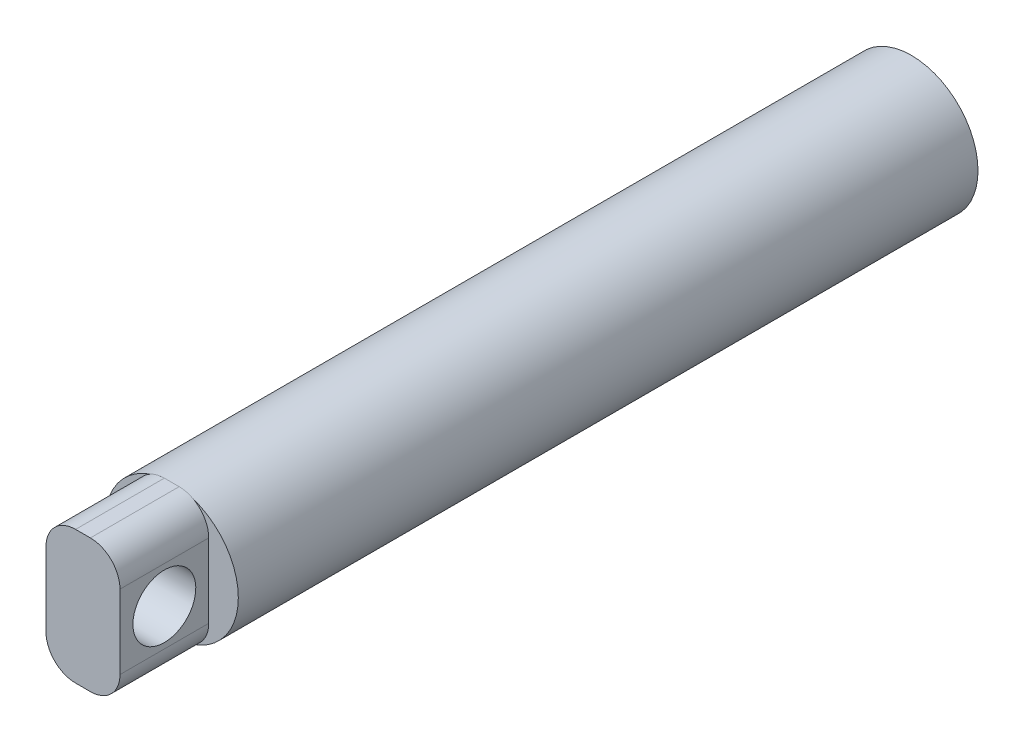
SolidWorks part; units mm, degrees
ref_plane "Plano frontal" through (0, 0, 0) normal (0, 0, 1) x (1, 0, 0)
ref_plane "Plano superior" through (0, 0, 0) normal (0, 1, 0) x (1, 0, 0)
ref_plane "Plano direito" through (0, 0, 0) normal (1, 0, 0) x (0, 0, -1)
sketch "Esboço1" plane through (0, 0, 0) normal (0, 0, 1) x (1, 0, 0)
  circle A0 centre (0, 0) radius 4.5
  dimension "D1" = 9
extrude "Ressalto-extrusão1" add sketch "Esboço1" along normal blind 50
sketch "Esboço2" plane through (0, 0, 50) normal (0, 0, 1) x (1, 0, 0)
  line L1 (-2.5, -4.5) -> (2.5, -4.5)
  line L2 (-2.5, -4.5) -> (-2.5, 4.5)
  line L3 (-2.5, 4.5) -> (2.5, 4.5)
  line L4 (2.5, -4.5) -> (2.5, 4.5)
  line L5 (-2.5, -4.5) -> (2.5, 4.5) construction
  line L6 (-2.5, 4.5) -> (2.5, -4.5) construction
  point P0 (0, 0)
  dimension "D1" = 4.5
  dimension "D2" = 5
extrude "Ressalto-extrusão2" add sketch "Esboço2" along normal blind 6
fillet "Filete1" radius 2 4 edges at (2.5, -4.5, 53) (-2.5, -4.5, 53) (2.5, 4.5, 53) (-2.5, 4.5, 53)
sketch "Esboço3" plane through (-2.5, 0, 0) normal (-1, 0, 0) x (0, 0, 1)
  line L0 (56, 2.5) -> (50, -2.5) construction
  circle A0 centre (53, 0) radius 2.125
  dimension "D1" = 4.25
extrude "Corte-extrusão1" cut sketch "Esboço3" against normal blind 6
